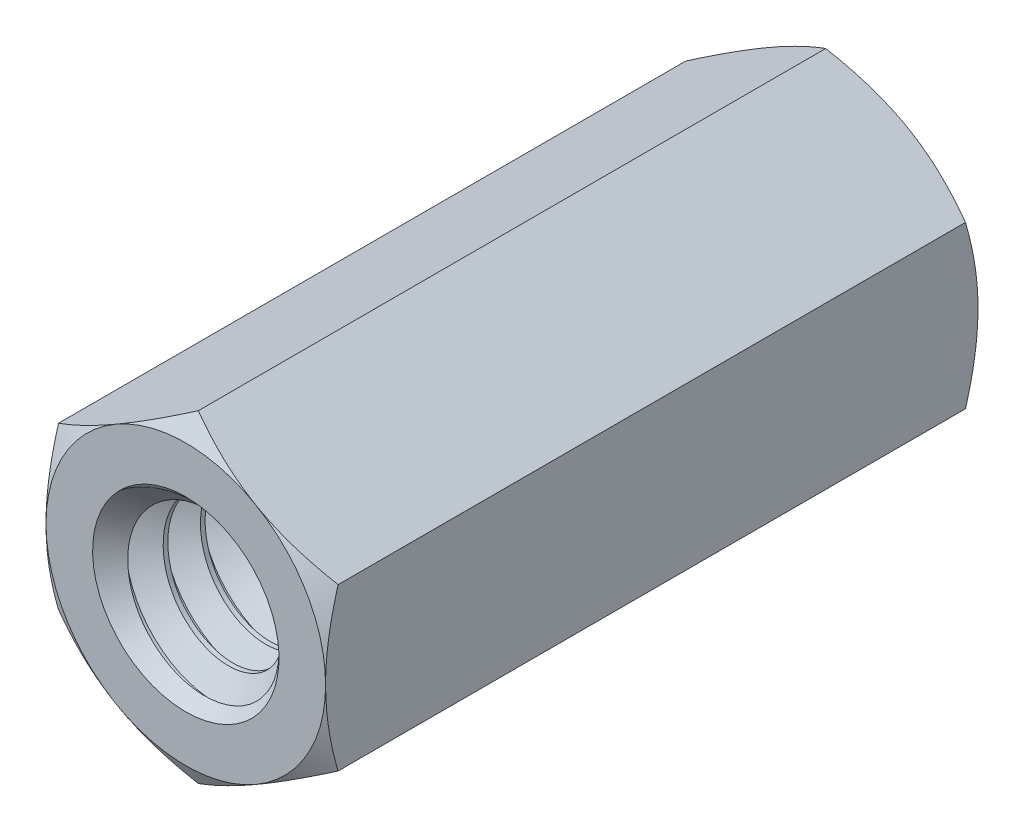
SolidWorks part; units mm, degrees
material "AISI 1020"
ref_plane "Front Plane" through (0, 0, 0) normal (0, 0, 1) x (1, 0, 0)
ref_plane "Top Plane" through (0, 0, 0) normal (0, 1, 0) x (1, 0, 0)
ref_plane "Right Plane" through (0, 0, 0) normal (1, 0, 0) x (0, 0, -1)
sketch "Sketch1" plane through (0, 0, 0) normal (1, 0, 0) x (0, 0, -1)
  line L0 (-11.1125, 0) -> (11.1125, 0) construction
  line L1 (0, 4.7625) -> (0, -4.7625) construction
  line L2 (-11.1125, 3.175) -> (-11.1125, -3.175) construction
  line L3 (11.1125, 3.175) -> (11.1125, -3.175) construction
  line L4 (-11.1125, 4.7625) -> (11.1125, 4.7625) construction
sketch "Sketch1a" plane through (0, 0, 0) normal (0, 0, 1) x (1, 0, 0)
  line L0 (0, 0) -> (-1.215, -2.9333) construction
  line L1 (0, 5.4993) -> (-4.7625, 2.7496)
  line L2 (-4.7625, 2.7496) -> (-4.7625, -2.7496)
  line L3 (-4.7625, -2.7496) -> (0, -5.4993)
  line L4 (0, -5.4993) -> (4.7625, -2.7496)
  line L5 (4.7625, -2.7496) -> (4.7625, 2.7496)
  line L6 (4.7625, 2.7496) -> (0, 5.4993)
  circle A0 centre (0, 0) radius 4.7625 construction
  circle A1 centre (0, 0) radius 3.175
  point P11 (-1.215, -2.9333)
  dimension "D1" = 22.5
extrude "Boss-Extrude1" add sketch "Sketch1a" against normal up to vertex (-11.1125 mm away) and the other way up to vertex (-11.1125 mm away) up to point (0, 0, 11.1125) other way up to point (0, 0, -11.1125)
sketch "Sketch2" plane through (0, 0, -11.1125) normal (0, 0, -1) x (-1, 0, 0)
  circle A0 centre (0, 0) radius 4.7625 construction
  circle A1 centre (0, 0) radius 4.7625
extrude "Cut-Extrude1" cut sketch "Sketch2" against normal through all draft 60 flip side to cut
sketch "Sketch3" plane through (0, 0, 11.1125) normal (0, 0, 1) x (1, 0, 0)
  circle A0 centre (0, 0) radius 4.7625 construction
  circle A1 centre (0, 0) radius 4.7625
extrude "Cut-Extrude2" cut sketch "Sketch3" against normal through all draft 60 flip side to cut
sketch "Sketch4" plane through (0, 0, 11.1125) normal (0, 0, 1) x (1, 0, 0)
  circle A0 centre (0, 0) radius 3.175 construction
  circle A1 centre (0, 0) radius 3.175
ref_axis "Center Axis 1" through (0, 0, -11.1125) along (0, 0, 1)
ref_plane "Contact Plane 1" through (0, 0, 11.1125) normal (0, 0, 1) x (1, 0, 0)
ref_plane "Contact Plane 2" through (0, 0, -11.1125) normal (0, 0, -1) x (-1, 0, 0)
curve "Helix/Spiral1" pitch 1.27 height 23.495 radius 3.175 centre (0, 0, 11.1125) axis (0, 0, -1) start towards (0, 1, 0) parameters "Pitch"=1.27
sketch "Sketch5" plane through (0, 0, 0) normal (1, 0, 0) x (0, 0, -1)
  line L0 (-11.0728, 3.2437) -> (-12.2634, 3.2437)
  line L1 (-12.2634, 3.2437) -> (-11.7475, 2.3501)
  line L2 (-11.5888, 2.3501) -> (-11.0728, 3.2437)
  line L6 (-12.3031, 3.3125) -> (-11.0331, 3.3125) construction
  line L7 (-12.3031, 3.3125) -> (-11.6681, 2.2126) construction
  line L8 (-11.6681, 2.2126) -> (-11.0331, 3.3125) construction
  line L9 (-12.2237, 3.175) -> (-11.1125, 3.175) construction
  line L10 (-11.6681, 3.3125) -> (-11.6681, 3.175) construction
  line L11 (-11.6681, 2.2126) -> (-11.6681, 2.3501) construction
  line L12 (-11.7475, 2.3501) -> (-11.5888, 2.3501)
  line L13 (-11.6681, 3.2437) -> (-11.0728, 3.2437) construction
  dimension "D4" = 1.27
  dimension "D5" = 0.1588
sweep "Sweep3" add profiles "Sketch5" path "Helix/Spiral1"
sketch "Sketch7" plane through (0, 0, 11.1125) normal (0, 0, 1) x (1, 0, 0)
  line L6 (0, 5.4993) -> (-4.7625, 2.7496)
  line L7 (-4.7625, 2.7496) -> (-4.7625, -2.7496)
  line L8 (-4.7625, -2.7496) -> (0, -5.4993)
  line L9 (0, -5.4993) -> (4.7625, -2.7496)
  line L10 (4.7625, -2.7496) -> (4.7625, 2.7496)
  line L11 (4.7625, 2.7496) -> (0, 5.4993)
  line L12 (0, 5.4993) -> (-4.7625, 2.7496)
  line L13 (-4.7625, 2.7496) -> (-4.7625, -2.7496)
  line L14 (-4.7625, -2.7496) -> (0, -5.4993)
  line L15 (0, -5.4993) -> (4.7625, -2.7496)
  line L16 (4.7625, -2.7496) -> (4.7625, 2.7496)
  line L17 (4.7625, 2.7496) -> (0, 5.4993)
  dimension "D2" = 0
extrude "Cut-Extrude3" cut sketch "Sketch7" along normal through all
sketch "Sketch8" plane through (0, 0, 11.1125) normal (0, 0, 1) x (1, 0, 0)
  circle A1 centre (0, 0) radius 3.175
  circle A2 centre (0, 0) radius 3.175
  dimension "D1" = 0
extrude "Cut-Extrude4" cut sketch "Sketch8" against normal through all draft 45
sketch "Sketch9" plane through (0, 0, -11.1125) normal (0, 0, -1) x (-1, 0, 0)
  line L6 (4.7625, 2.7496) -> (0, 5.4993)
  line L7 (4.7625, -2.7496) -> (4.7625, 2.7496)
  line L8 (0, -5.4993) -> (4.7625, -2.7496)
  line L9 (-4.7625, -2.7496) -> (0, -5.4993)
  line L10 (-4.7625, 2.7496) -> (-4.7625, -2.7496)
  line L11 (0, 5.4993) -> (-4.7625, 2.7496)
  line L12 (4.7625, 2.7496) -> (0, 5.4993)
  line L13 (4.7625, -2.7496) -> (4.7625, 2.7496)
  line L14 (0, -5.4993) -> (4.7625, -2.7496)
  line L15 (-4.7625, -2.7496) -> (0, -5.4993)
  line L16 (-4.7625, 2.7496) -> (-4.7625, -2.7496)
  line L17 (0, 5.4993) -> (-4.7625, 2.7496)
  dimension "D1" = 0
extrude "Cut-Extrude5" cut sketch "Sketch9" along normal through all
sketch "Sketch10" plane through (0, 0, -11.1125) normal (0, 0, -1) x (-1, 0, 0)
  circle A1 centre (0, 0) radius 3.175
  circle A2 centre (0, 0) radius 3.175
  dimension "D1" = 0
extrude "Cut-Extrude6" cut sketch "Sketch10" against normal through all draft 45
equation "\"D3@Helix/Spiral1\"=\"Pitch@Helix/Spiral1\"+\"Length@Sketch1\""
equation "\"D4@Sketch5\"=\"Pitch@Helix/Spiral1\""
equation "\"D5@Sketch5\"=\"Pitch@Helix/Spiral1\"*.125"
